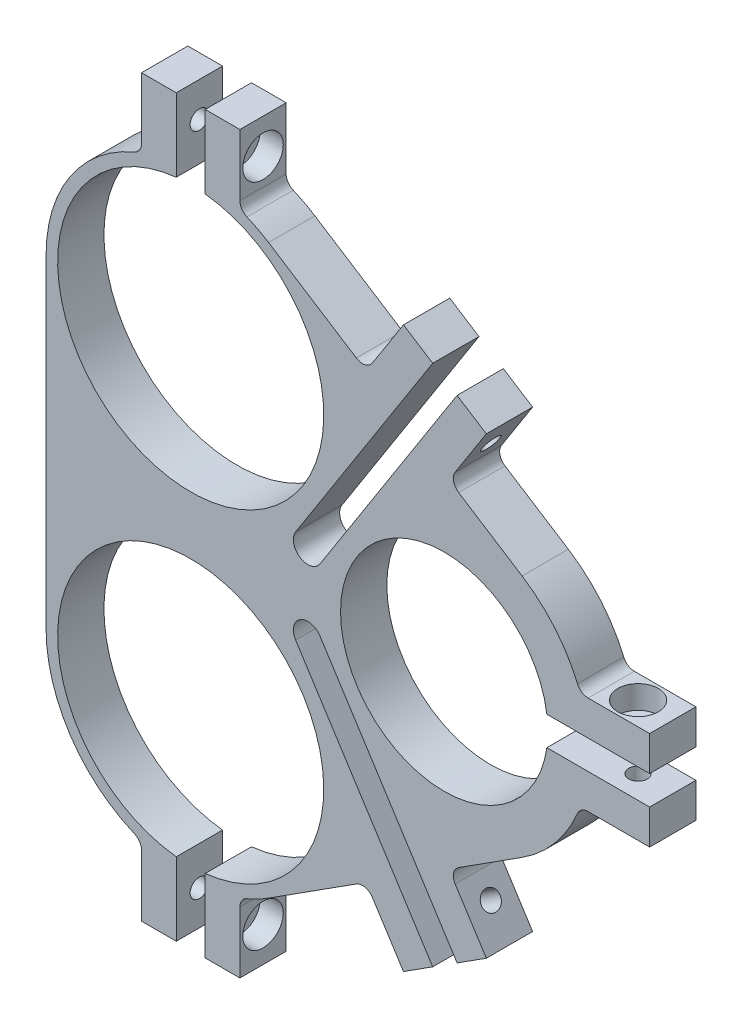
SolidWorks part; units mm, degrees
ref_plane "Front Plane" through (0, 0, 0) normal (0, 0, 1) x (1, 0, 0)
ref_plane "Top Plane" through (0, 0, 0) normal (0, 1, 0) x (1, 0, 0)
ref_plane "Right Plane" through (0, 0, 0) normal (1, 0, 0) x (0, 0, -1)
sketch "Sketch1" plane through (0, 0, 0) normal (0, 0, 1) x (1, 0, 0)
  line L0 (-39.6875, 88.9) -> (-39.6875, 0)
  line L1 (-39.6875, 44.45) -> (69.5608, 44.45) construction
  line L2 (21.3702, 122.3427) -> (48.1243, 105.2465)
  line L3 (3.9688, -36.2962) -> (3.9688, -56.3731)
  line L4 (0, 88.9) -> (0, 0) construction
  line L5 (-13.4938, -37.3231) -> (-13.4938, -56.3731)
  line L6 (3.9688, -56.3731) -> (13.4938, -56.3731)
  line L7 (-3.9688, -56.3731) -> (-13.4938, -56.3731)
  line L8 (13.4938, -37.3231) -> (13.4938, -56.3731)
  line L9 (-3.9687, -36.2962) -> (-3.9688, -56.3731)
  line L10 (21.3702, -33.4427) -> (48.1243, -16.3465)
  line L11 (13.4938, 126.2231) -> (13.4938, 145.2731)
  line L12 (-3.9688, 145.2731) -> (-13.4938, 145.2731)
  line L13 (3.9688, 145.2731) -> (13.4938, 145.2731)
  line L14 (3.9688, 145.2731) -> (3.9688, 125.1962)
  line L15 (-13.4938, 126.2231) -> (-13.4938, 145.2731)
  line L16 (56.1506, 100.1177) -> (62.8391, 95.8436) construction
  line L17 (56.1506, 100.1177) -> (28.7967, 57.3111)
  line L18 (-3.9688, 145.2731) -> (-3.9688, 125.1962)
  line L19 (62.8391, 95.8436) -> (35.4853, 53.037)
  line L20 (28.7967, 57.3111) -> (35.4853, 53.037) construction
  line L21 (56.1506, -11.2177) -> (28.7967, 31.5889)
  line L22 (56.1506, 100.1177) -> (66.4083, 116.1702)
  line L23 (3.9688, 145.2731) -> (-3.9688, 145.2731) construction
  line L24 (48.1243, 105.2465) -> (58.382, 121.299)
  line L25 (3.9688, -56.3731) -> (-3.9688, -56.3731) construction
  line L26 (66.4083, 116.1702) -> (58.382, 121.299)
  line L27 (32.141, 55.174) -> (59.4948, 97.9807) construction
  line L28 (62.8391, 95.8436) -> (73.0968, 111.8961)
  line L29 (73.0968, 111.8961) -> (81.123, 106.7673)
  line L30 (70.8654, 90.7148) -> (81.123, 106.7673)
  line L31 (70.8654, 90.7148) -> (90.931, 77.8927)
  line L32 (62.8391, -6.9436) -> (35.4853, 35.863)
  line L33 (70.8654, -1.8148) -> (81.123, -17.8673)
  line L34 (73.0968, -22.9961) -> (81.123, -17.8673)
  line L35 (62.8391, -6.9436) -> (73.0968, -22.9961)
  line L36 (56.1506, -11.2177) -> (66.4083, -27.2702)
  line L37 (66.4083, -27.2702) -> (58.382, -32.399)
  line L38 (48.1243, -16.3465) -> (58.382, -32.399)
  line L39 (32.141, 33.726) -> (59.4948, -9.0807) construction
  line L40 (56.1506, -11.2177) -> (62.8391, -6.9436) construction
  line L41 (70.8654, -1.8148) -> (90.931, 11.0073)
  line L42 (97.7306, 48.4187) -> (125.9339, 48.4187)
  line L43 (125.9339, 48.4187) -> (125.9339, 57.9437)
  line L44 (125.9339, 57.9437) -> (106.8839, 57.9437)
  line L45 (97.7306, 40.4812) -> (125.9339, 40.4812)
  line L46 (125.9339, 40.4812) -> (125.9339, 30.9563)
  line L47 (125.9339, 30.9563) -> (106.8839, 30.9562)
  arc A0 (3.9688, -36.2962) -> (-3.9687, -36.2962) centre (0, 0) ccw
  arc A1 (-3.9688, 125.1962) -> (3.9688, 125.1962) centre (0, 88.9) ccw
  arc A2 (13.4938, 126.2231) -> (21.3702, 122.3427) centre (0, 88.9) cw
  arc A3 (-39.6875, 0) -> (-13.4938, -37.3231) centre (0, 0) ccw
  arc A4 (97.7306, 48.4187) -> (97.7306, 40.4812) centre (69.5608, 44.45) ccw
  arc A5 (13.4938, -37.3231) -> (21.3702, -33.4427) centre (0, 0) ccw
  arc A6 (-39.6875, 88.9) -> (-13.4938, 126.2231) centre (0, 88.9) cw
  arc A7 (106.8839, 57.9437) -> (106.8839, 30.9562) centre (69.5608, 44.45) ccw construction
  circle A8 centre (0, 0) radius 36.5125 construction
  circle A9 centre (0, 88.9) radius 36.5125 construction
  circle A10 centre (0, 0) radius 39.6875 construction
  circle A11 centre (69.5608, 44.45) radius 36.5125 construction
  circle A12 centre (0, 88.9) radius 39.6875 construction
  arc A13 (90.931, 77.8927) -> (106.8839, 57.9437) centre (69.5608, 44.45) cw
  circle A14 centre (32.141, 55.174) radius 3.9687 construction
  arc A15 (28.7967, 57.3111) -> (35.4853, 53.037) centre (32.141, 55.174) ccw
  circle A16 centre (32.141, 33.726) radius 3.9687 construction
  arc A17 (28.7967, 31.5889) -> (35.4853, 35.863) centre (32.141, 33.726) cw
  arc A18 (106.8839, 30.9562) -> (90.931, 11.0073) centre (69.5608, 44.45) cw
  point P14 (0, 36.5125)
  dimension "D2" = 56.896
  dimension "D4" = 73.025
  dimension "D5" = 73.025
  dimension "D7" = 79.375
  dimension "D9" = 79.375
  dimension "D10" = 73.025
  dimension "D11" = 7.9375
  dimension "D1" = 7.9375
  dimension "D3" = 88.9
  dimension "D6" = 9.525
  dimension "D8" = 19.05
  dimension "D12" = 82.55
  dimension "D13" = 41.275
  dimension "D14" = 50.8
  dimension "D15" = 19.05
  dimension "D16" = 9.525
  dimension "D17" = 9.525
  dimension "D18" = 7.9375
  dimension "D19" = 19.05
extrude "Extrude1" add sketch "Sketch1" along normal mid plane 12.7
hole_wizard "CBORE for 1/4 Socket Head Cap Screw1" positions "Sketch3" profile "Sketch2" counterbore size "1/4" standard "Ansi Inch" end condition up to next
sketch "Sketch3" plane through (13.4938, 0, 0) normal (1, 0, 0) x (0, 0, -1)
  line L0 (6.35, 145.2731) -> (-6.35, 126.2231) construction
  point P0 (0, 135.7481)
sketch "Sketch2" plane through (13.4938, 135.7481, 0) normal (0, 1, 0) x (0, 0, -1)
  line L0 (0, 0) -> (0, 9.525)
  line L1 (0, 9.525) -> (3.3782, 9.525)
  line L3 (3.3782, 9.525) -> (3.3782, 6.35)
  line L4 (3.3782, 6.35) -> (5.5562, 6.35)
  line L5 (5.5562, 6.35) -> (5.5562, 0)
  line L7 (5.5562, 0) -> (0, 0)
  line L11 (0, -6.35) -> (0, 107.95) construction
  dimension "Thru Hole Dia." = 6.7564
  dimension "Thru Hole Depth" = 9.525
  dimension "C'Bore Dia." = 11.1125
  dimension "C'Bore Depth" = 6.35
hole_wizard "1/4-20 Tapped Hole1" positions "Sketch5" profile "Sketch4" tap size "1/4-20" standard "Ansi Inch" end condition through all
sketch "Sketch5" plane through (-3.9688, 0, 0) normal (1, 0, 0) x (0, 0, -1)
  point P0 (0, 135.7481)
sketch "Sketch4" plane through (-3.9688, 135.7481, 0) normal (0, 1, 0) x (0, 0, -1)
  line L0 (0, 0) -> (0, 35.7188)
  line L1 (0, 35.7188) -> (2.5527, 35.7188)
  line L2 (2.5527, 35.7188) -> (2.5527, 0)
  line L5 (2.5527, 0) -> (0, 0)
  line L11 (0, -6.35) -> (0, 107.95) construction
  dimension "Thru Tap Drill Dia." = 5.1054
  dimension "Thru Tap Drill Depth" = 35.7188
cosmetic thread "Hole Thread1" parameters "D2"=6.35
hole_wizard "CBORE for 1/4 Socket Head Cap Screw3" positions "Sketch16" profile "Sketch17" counterbore size "1/4" standard "Ansi Inch" end condition up to next
sketch "Sketch16" plane through (13.4938, 0, 0) normal (1, 0, 0) x (0, 0, -1)
  line L0 (6.35, -37.3231) -> (-6.35, -56.3731) construction
  point P0 (0, -46.8481)
sketch "Sketch17" plane through (13.4938, -46.8481, 0) normal (0, 1, 0) x (0, 0, -1)
  line L0 (0, 0) -> (0, 9.525)
  line L1 (0, 9.525) -> (3.3782, 9.525)
  line L3 (3.3782, 9.525) -> (3.3782, 6.35)
  line L4 (3.3782, 6.35) -> (5.5562, 6.35)
  line L5 (5.5562, 6.35) -> (5.5562, 0)
  line L7 (5.5562, 0) -> (0, 0)
  line L11 (0, -6.35) -> (0, 107.95) construction
  dimension "Thru Hole Dia." = 6.7564
  dimension "Thru Hole Depth" = 9.525
  dimension "C'Bore Dia." = 11.1125
  dimension "C'Bore Depth" = 6.35
hole_wizard "1/4-20 Tapped Hole4" positions "Sketch19" profile "Sketch21" tap size "1/4-20" standard "Ansi Inch" end condition through all
sketch "Sketch19" plane through (-3.9687, 0, 0) normal (1, 0, 0) x (0, 0, -1)
  point P0 (0, -46.8481)
sketch "Sketch21" plane through (-3.9687, -46.8481, 0) normal (0, 1, 0) x (0, 0, -1)
  line L0 (0, 0) -> (0, 35.7188)
  line L1 (0, 35.7188) -> (2.5527, 35.7188)
  line L2 (2.5527, 35.7188) -> (2.5527, 0)
  line L5 (2.5527, 0) -> (0, 0)
  line L11 (0, -6.35) -> (0, 107.95) construction
  dimension "Thru Tap Drill Dia." = 5.1054
  dimension "Thru Tap Drill Depth" = 35.7188
cosmetic thread "Hole Thread4" parameters "D2"=6.35
sketch "Sketch29" plane through (9.1581, -5.8521, 0) normal (0.8427, -0.5385, 0) x (0, 0, -1)
  line L0 (6.35, 133.6491) -> (-6.35, 114.5991) construction
hole_wizard "Tap Drill for 1/4-20 Tap1" positions "Sketch30" profile "Sketch31" hole size "1/4-20" standard "ANSI Inch" end condition up to next
sketch "Sketch30" plane through (9.1581, -5.8521, 0) normal (0.8427, -0.5385, 0) x (0, 0, -1)
  line L0 (6.35, 133.6491) -> (-6.35, 114.5991) construction
  point P0 (0, 124.1241)
sketch "Sketch31" plane through (75.9942, 98.741, 0) normal (0, 0, 1) x (0.5385, 0.8427, 0)
  line L0 (0, 0) -> (0, 9.525)
  line L1 (0, 9.525) -> (2.5527, 9.525)
  line L2 (2.5527, 9.525) -> (2.5527, 0)
  line L5 (2.5527, 0) -> (0, 0)
  line L11 (0, -6.35) -> (0, 107.95) construction
  dimension "Thru Hole Dia." = 5.1054
  dimension "Thru Hole Depth" = 9.525
sketch "Sketch41" plane through (0, 57.9437, 0) normal (0, 1, 0) x (1, 0, 0)
  line L0 (125.9339, 6.35) -> (106.8839, -6.35) construction
hole_wizard "CBORE for 1/4 Socket Head Cap Screw6" positions "Sketch42" profile "Sketch43" counterbore size "1/4" standard "ANSI Inch" end condition up to next
sketch "Sketch42" plane through (0, 57.9437, 0) normal (0, 1, 0) x (1, 0, 0)
  line L0 (125.9339, 6.35) -> (106.8839, -6.35) construction
  point P0 (116.4089, 0)
sketch "Sketch43" plane through (116.4089, 57.9437, 0) normal (1, 0, 0) x (0, 0, 1)
  line L0 (0, 0) -> (0, 9.525)
  line L1 (0, 9.525) -> (3.3782, 9.525)
  line L3 (3.3782, 9.525) -> (3.3782, 6.35)
  line L4 (3.3782, 6.35) -> (5.5562, 6.35)
  line L5 (5.5562, 6.35) -> (5.5563, 0)
  line L7 (5.5563, 0) -> (0, 0)
  line L11 (0, -6.35) -> (0, 107.95) construction
  dimension "Thru Hole Dia." = 6.7564
  dimension "Thru Hole Depth" = 9.525
  dimension "C'Bore Dia." = 11.1125
  dimension "C'Bore Depth" = 6.35
hole_wizard "1/4-20 Tapped Hole7" positions "Sketch44" profile "Sketch45" tap size "1/4-20" standard "ANSI Inch" end condition up to next
sketch "Sketch44" plane through (0, 40.4813, 0) normal (0, 1, 0) x (1, 0, 0)
  line L0 (125.9339, 6.35) -> (106.8839, -6.35) construction
  point P0 (116.4089, 0)
sketch "Sketch45" plane through (116.4089, 40.4813, 0) normal (1, 0, 0) x (0, 0, 1)
  line L0 (0, 0) -> (0, 9.525)
  line L1 (0, 9.525) -> (2.5527, 9.525)
  line L2 (2.5527, 9.525) -> (2.5527, 0)
  line L5 (2.5527, 0) -> (0, 0)
  line L11 (0, -6.35) -> (0, 107.95) construction
  dimension "Thru Tap Drill Dia." = 5.1054
  dimension "Thru Tap Drill Depth" = 9.525
cosmetic thread "Hole Thread7" parameters "D2"=6.35
sketch "Sketch46" plane through (49.4952, 31.6279, 0) normal (0.8427, 0.5385, 0) x (0, 0, -1)
  line L0 (-6.35, -39.6875) -> (6.35, -58.7375) construction
hole_wizard "Tap Drill for 1/4-20 Tap2" positions "Sketch47" profile "Sketch48" hole size "1/4-20" standard "ANSI Inch" end condition up to next
sketch "Sketch47" plane through (49.4952, 31.6279, 0) normal (0.8427, 0.5385, 0) x (0, 0, -1)
  line L0 (-6.35, -39.6875) -> (6.35, -58.7375) construction
  point P0 (0, -49.2125)
sketch "Sketch48" plane through (75.9942, -9.841, 0) normal (0, 0, 1) x (-0.5385, 0.8427, 0)
  line L0 (0, 0) -> (0, 9.525)
  line L1 (0, 9.525) -> (2.5527, 9.525)
  line L2 (2.5527, 9.525) -> (2.5527, 0)
  line L5 (2.5527, 0) -> (0, 0)
  line L11 (0, -6.35) -> (0, 107.95) construction
  dimension "Thru Hole Dia." = 5.1054
  dimension "Thru Hole Depth" = 9.525
fillet "Fillet1" radius 3.175 10 edges at (13.4938, 126.2231, 0) (-13.4938, 126.2231, 0) (-13.4938, -37.3231, 0) (13.4938, -37.3231, 0) (48.1243, 105.2465, 0) (70.8654, 90.7148, 0) (106.8839, 30.9563, 0) (106.8839, 57.9437, 0) (48.1243, -16.3465, 0) (70.8654, -1.8148, 0)
